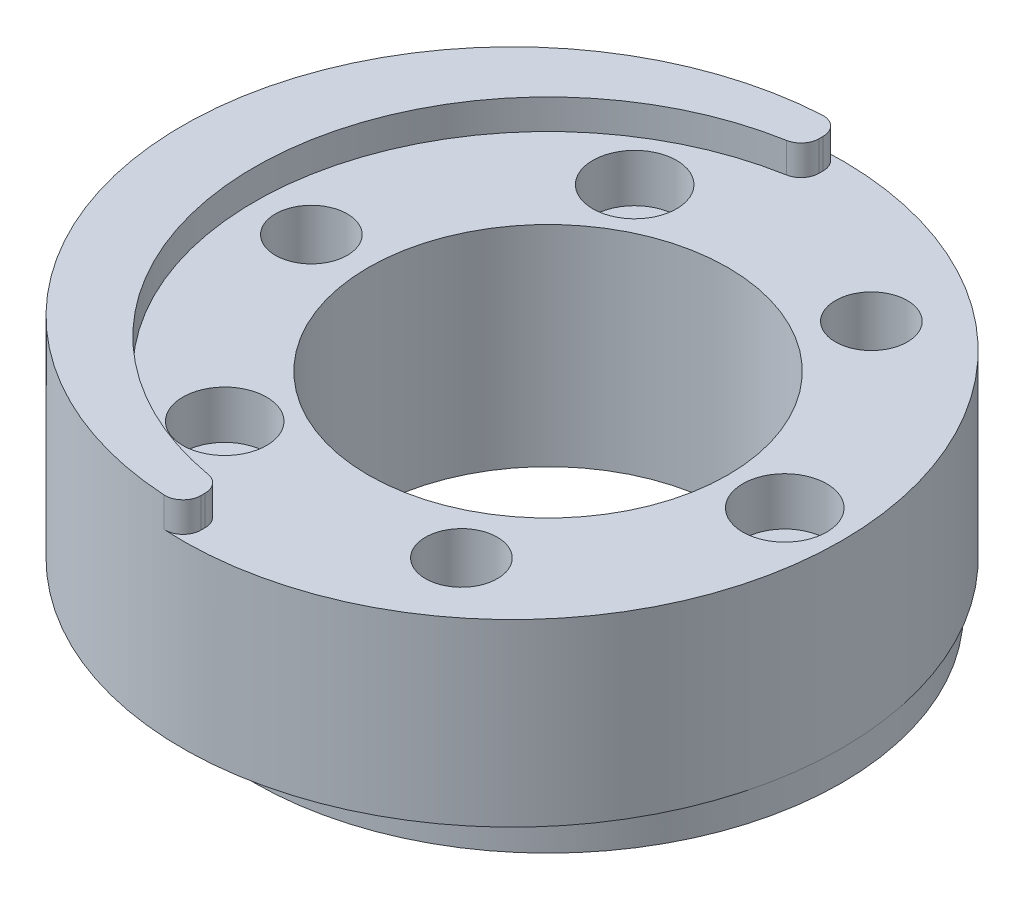
SolidWorks part; units mm, degrees
ref_plane "Front Plane" through (0, 0, 0) normal (0, 0, 1) x (1, 0, 0)
ref_plane "Top Plane" through (0, 0, 0) normal (0, 1, 0) x (1, 0, 0)
ref_plane "Right Plane" through (0, 0, 0) normal (1, 0, 0) x (0, 0, -1)
sketch "Sketch1" plane through (0, 0, 0) normal (0, 1, 0) x (1, 0, 0)
  circle A0 centre (0, 0) radius 27.5
extrude "Boss-Extrude1" add sketch "Sketch1" along normal blind 15
sketch "Sketch3" plane through (0, 15, 0) normal (0, 1, 0) x (1, 0, 0)
  line L0 (0, 0) -> (3, 0)
  line L1 (0, 0) -> (0, 27.5)
  line L2 (0, 0) -> (0, -27.5)
  circle A0 centre (3, 0) radius 24.5
  circle A1 centre (0, 0) radius 27.5
  point P5 (0, 24.3156)
  point P9 (0, -24.3156)
  circle M3 centre (0, 0) radius 27.5
extrude "Boss-Extrude3" add sketch "Sketch3" along normal blind 2.5 contours A0 L1 L2 M3 region at (-22.1149, 15, 0)
fillet "Fillet2" radius 1.5 4 edges at (0, 16.25, -27.5) (0, 16.25, -24.3156) (0, 16.25, 24.3156) (0, 16.25, 27.5)
sketch "Sketch4" plane through (0, 15, 0) normal (0, 1, 0) x (1, 0, 0)
  line L0 (0, 0) -> (3, 0)
  line L1 (-12, 0) -> (-21.5, 0)
  circle A2 centre (3, 0) radius 15
  arc A3 (-1.2404, 24.1303) -> (-1.2404, -24.1303) centre (3, 0) ccw construction
  circle A4 centre (-16.75, 0) radius 3
  circle A5 centre (12.875, 17.104) radius 3
  circle A6 centre (12.875, -17.104) radius 3
  point P23 (3, 0)
  dimension "D1" = 3
extrude "Cut-Extrude1" cut sketch "Sketch4" against normal blind 5 contours L1 A4 | L1 A4 | A5 | A6 region at (-16.75, 15, 1.2732) region at (-16.75, 15, -1.2732) region at (12.875, 15, -17.104) region at (12.875, 15, 17.104)
sketch "Sketch5" plane through (0, 15, 0) normal (0, 1, 0) x (1, 0, 0)
  line L0 (0, 0) -> (3, 0)
  circle A0 centre (3, 0) radius 15
extrude "Cut-Extrude2" cut sketch "Sketch5" against normal blind 15 contours A0 region at (-11.5757, 15, 0)
sketch "Sketch7" plane through (0, 0, 0) normal (0, -1, 0) x (1, 0, 0)
  line L0 (0, 0) -> (3, 0)
  line L1 (0, -27.5) -> (0, 27.5)
  circle A0 centre (3, 0) radius 24.5
  circle A1 centre (0, 0) radius 27.5 construction
  circle M2 centre (3, 0) radius 15
extrude "Boss-Extrude6" add sketch "Sketch7" along normal blind 2.5 contours A0 L1 M2 | L1 A0 M2 region at (-20.9683, 0, 0) region at (0.5619, 0, -19.5063)
sketch "Sketch8" plane through (0, 15, 0) normal (0, 1, 0) x (1, 0, 0)
  line L0 (0, 0) -> (3, 0)
  line L1 (1.5, 2.5981) -> (3, 0)
  line L2 (4.5, 2.5981) -> (3, 0)
  line L3 (6, 0) -> (3, 0)
  line L4 (4.5, -2.5981) -> (3, 0)
  line L5 (1.5, -2.5981) -> (3, 0)
  circle A0 centre (-16.75, 0) radius 2
  circle A1 centre (-6.875, 17.104) radius 2
  circle A2 centre (12.875, 17.104) radius 2
  circle A3 centre (22.75, 0) radius 2
  circle A4 centre (12.875, -17.104) radius 2
  circle A5 centre (-6.875, -17.104) radius 2
  point P6 (0, 0)
  point P23 (3, 0)
extrude "Cut-Extrude3" cut sketch "Sketch8" against normal blind 17.5 contours A1 | A5 | A3 region at (-6.875, 15, -17.104) region at (22.75, 15, 0) region at (-6.875, 15, 17.104)
sketch "Sketch9" plane through (0, 15, 0) normal (0, 1, 0) x (1, 0, 0)
  line L0 (0, 0) -> (3, 0)
  circle A0 centre (-6.875, 17.104) radius 3.5
  circle A1 centre (22.75, 0) radius 3.5
  circle A2 centre (-6.875, -17.104) radius 3.5
  point P12 (3, 0)
  circle M2 centre (-6.875, 17.104) radius 2
  circle M3 centre (-6.875, -17.104) radius 2
  circle M4 centre (22.75, 0) radius 2
extrude "Cut-Extrude4" cut sketch "Sketch9" against normal blind 4 contours A0 M2 | A1 M4 | A2 M3 region at (-10.276, 15, -17.104) region at (19.349, 15, 0) region at (-10.276, 15, 17.104)
sketch "Sketch10" plane through (0, 10, 0) normal (0, 1, 0) x (1, 0, 0)
  line L0 (0, 0) -> (3, 0)
  circle A0 centre (-16.75, 0) radius 2
  circle A1 centre (12.875, 17.104) radius 2
  circle A2 centre (12.875, -17.104) radius 2
  point P12 (3, 0)
extrude "Cut-Extrude5" cut sketch "Sketch10" against normal blind 2.5 contours A0 | A1 | A2 region at (-16.75, 10, 0) region at (12.875, 10, -17.104) region at (12.875, 10, 17.104)
